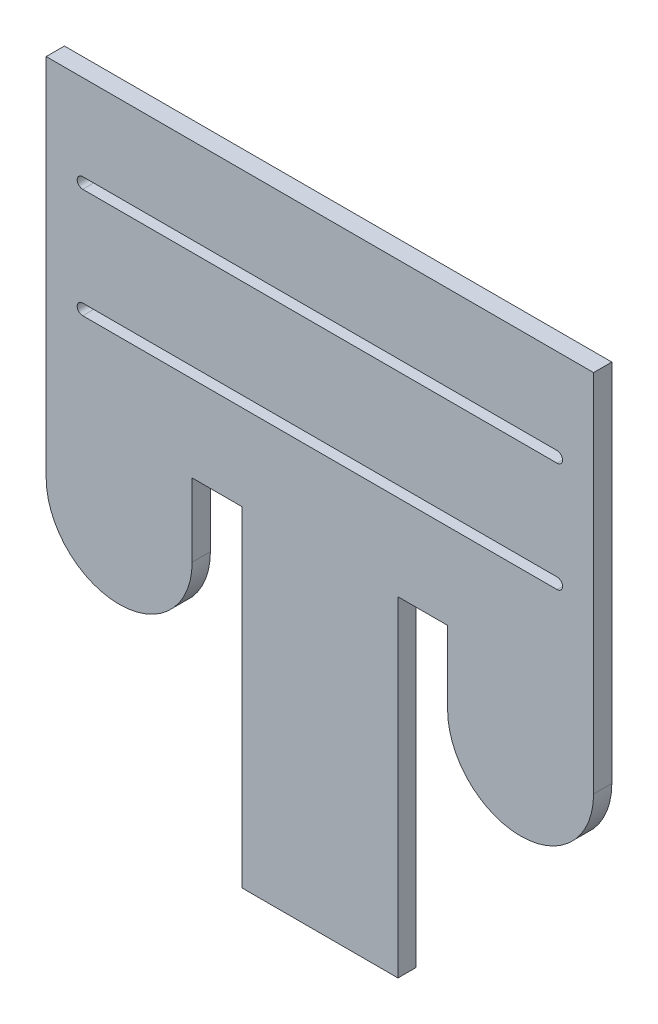
SolidWorks part; units mm, degrees
material "6061 Alloy"
ref_plane "Front Plane" through (0, 0, 0) normal (0, 0, 1) x (1, 0, 0)
ref_plane "Top Plane" through (0, 0, 0) normal (0, 1, 0) x (1, 0, 0)
ref_plane "Right Plane" through (0, 0, 0) normal (1, 0, 0) x (0, 0, -1)
sketch "Sketch1" plane through (0, 0, 0) normal (0, 1, 0) x (1, 0, 0)
  line L1 (0, 0) -> (190.5, 0)
  line L2 (0, 0) -> (0, 6.35)
  line L3 (0, 6.35) -> (190.5, 6.35)
  line L4 (190.5, 0) -> (190.5, 6.35)
  dimension "D1" = 190.5
  dimension "D2" = 6.35
extrude "Boss-Extrude1" add sketch "Sketch1" along normal blind 101.6
sketch "Sketch2" plane through (0, 0, -6.35) normal (0, 0, -1) x (-1, 0, 0)
  line L0 (-177.8, 71.755) -> (-12.7, 71.755)
  line L1 (-177.8, 67.945) -> (-12.7, 67.945)
  line L2 (-190.5, 0) -> (0, 0) construction
  line L3 (-179.705, 69.85) -> (-10.795, 69.85) construction
  line L4 (-190.5, 50.8) -> (0, 50.8) construction
  line L5 (-190.5, 101.6) -> (-190.5, 0) construction
  line L6 (0, 101.6) -> (0, 0) construction
  line L9 (-177.8, 33.655) -> (-12.7, 33.655)
  line L10 (-177.8, 29.845) -> (-12.7, 29.845)
  arc A0 (-12.7, 71.755) -> (-12.7, 67.945) centre (-12.7, 69.85) cw
  arc A1 (-177.8, 71.755) -> (-177.8, 67.945) centre (-177.8, 69.85) ccw
  arc A2 (-12.7, 29.845) -> (-12.7, 33.655) centre (-12.7, 31.75) ccw
  arc A3 (-177.8, 29.845) -> (-177.8, 33.655) centre (-177.8, 31.75) cw
  point P8 (-95.25, 0)
  point P9 (-95.25, 67.945)
  dimension "D1" = 3.81
  dimension "D2" = 165.1
  dimension "D3" = 69.85
extrude "Cut-Extrude1" cut sketch "Sketch2" against normal through all
sketch "Sketch3" plane through (0, 0, 0) normal (0, 0, 1) x (1, 0, 0)
  line L0 (0, 0) -> (190.5, 0) construction
  line L1 (0, 0) -> (50.8, 0)
  line L2 (0, 0) -> (0, -50.8)
  line L3 (0, -50.8) -> (50.8, -50.8)
  line L4 (50.8, 0) -> (50.8, -50.8)
  line L5 (190.5, 0) -> (0, 0) construction
  line L6 (190.5, 101.6) -> (190.5, 0) construction
  line L7 (95.25, 0) -> (95.25, -50.8) construction
  line L8 (190.5, 0) -> (139.7, 0)
  line L9 (190.5, 0) -> (190.5, -50.8)
  line L10 (190.5, -50.8) -> (139.7, -50.8)
  line L11 (139.7, 0) -> (139.7, -50.8)
  dimension "D1" = 50.8
  dimension "D2" = 50.8
  dimension "D3" = 50.8
extrude "Boss-Extrude2" add sketch "Sketch3" against normal up to surface (6.35 mm away) up to face at (95.25, 69.85, -6.35)
fillet "Fillet1" radius 25.4 4 edges at (139.7, -50.8, -3.175) (0, -50.8, -3.175) (50.8, -50.8, -3.175) (190.5, -50.8, -3.175)
sketch "Sketch4" plane through (0, 0, 0) normal (0, -1, 0) x (1, 0, 0)
  line L0 (95.25, -6.35) -> (95.25, 0) construction
  line L1 (139.7, -6.35) -> (50.8, -6.35) construction
  line L2 (50.8, 0) -> (139.7, 0) construction
  line L4 (68.072, 0) -> (122.428, 0)
  line L5 (68.072, 0) -> (68.072, -6.35)
  line L6 (68.072, -6.35) -> (122.428, -6.35)
  line L7 (122.428, 0) -> (122.428, -6.35)
  dimension "D1" = 27.178
  dimension "D2" = 27.178
extrude "Boss-Extrude3" add sketch "Sketch4" along normal up to surface (114.9016 mm away)
